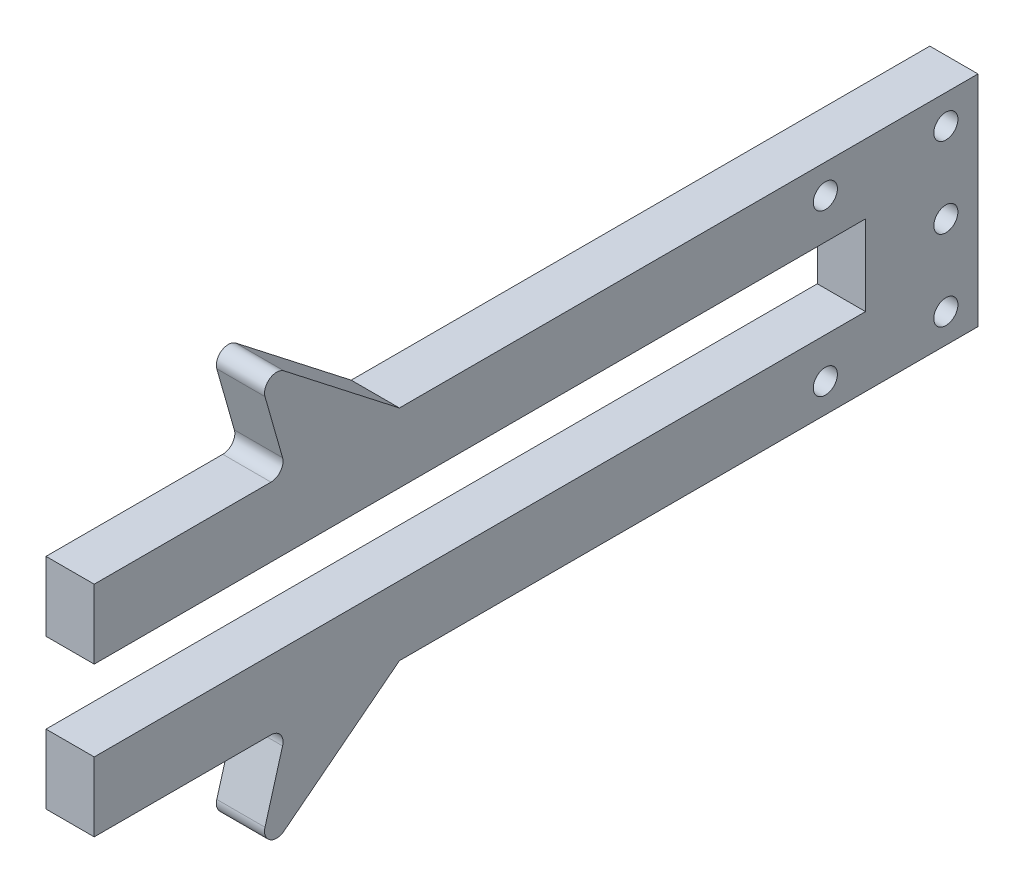
SolidWorks part; units mm, degrees
material "Custom Plastic"
ref_plane "Front Plane" through (0, 0, 0) normal (0, 0, 1) x (1, 0, 0)
ref_plane "Top Plane" through (0, 0, 0) normal (0, 1, 0) x (1, 0, 0)
ref_plane "Right Plane" through (0, 0, 0) normal (1, 0, 0) x (0, 0, -1)
sketch "Sketch2" plane through (0, 0, 0) normal (1, 0, 0) x (0, 0, -1)
  line L0 (-20.9136, -4.3885) -> (-8.9196, -4.3885)
  line L1 (34.0864, -4.3885) -> (34.0864, -18.0092)
  line L2 (34.0864, -18.0092) -> (-1.9196, -18.0092)
  line L3 (-20.9136, -18.0092) -> (-20.9136, -13.6989)
  line L4 (-20.9136, -13.6989) -> (27.0864, -13.6989)
  line L5 (27.0864, -13.6989) -> (27.0864, -8.6989)
  line L6 (27.0864, -8.6989) -> (-20.9136, -8.6989)
  line L7 (-20.9136, -8.6989) -> (-20.9136, -4.3885)
  line L8 (-1.9196, -4.3885) -> (-10.9136, 2.6115)
  line L9 (-10.9136, 2.6115) -> (-8.9196, -4.3885)
  line L10 (34.0864, -11.1989) -> (-19.6352, -11.1989) construction
  line L11 (-10.9136, -25.0092) -> (-8.9196, -18.0092)
  line L12 (-1.9196, -18.0092) -> (-10.9136, -25.0092)
  line L13 (-1.9196, -4.3885) -> (34.0864, -4.3885)
  line L14 (-8.9196, -18.0092) -> (-20.9136, -18.0092)
  dimension "D1" = 5
  dimension "D2" = 7
  dimension "D3" = 55
  dimension "D4" = 7
  dimension "D5" = 7
  dimension "D6" = 10
extrude "Boss-Extrude1" add sketch "Sketch2" along normal blind 3
fillet "Fillet1" radius 0.75 4 edges at (1.5, -25.0092, 10.9136) (1.5, -18.0092, 8.9196) (1.5, -4.3885, 8.9196) (1.5, 2.6115, 10.9136)
sketch "Sketch3" plane through (3, 0, 0) normal (1, 0, 0) x (0, 0, -1)
  line L0 (32.0864, -6.1989) -> (32.0864, -16.1989) construction
  line L1 (27.0864, -8.6989) -> (27.0864, -13.6989) construction
  line L2 (27.0864, -11.1989) -> (32.0864, -11.1989) construction
  line L3 (32.0864, -6.1989) -> (24.5864, -6.1989) construction
  line L4 (32.0864, -16.1989) -> (24.5864, -16.1989) construction
  circle A0 centre (32.0864, -6.1989) radius 0.75
  circle A1 centre (32.0864, -16.1989) radius 0.75
  circle A2 centre (32.0864, -11.1989) radius 0.75
  circle A3 centre (24.5864, -6.1989) radius 0.75
  circle A4 centre (24.5864, -16.1989) radius 0.75
  dimension "D3" = 1.5
  dimension "D1" = 5
  dimension "D2" = 10
  dimension "D4" = 7.5
  dimension "D5" = 7.5
extrude "Cut-Extrude1" cut sketch "Sketch3" against normal through all
